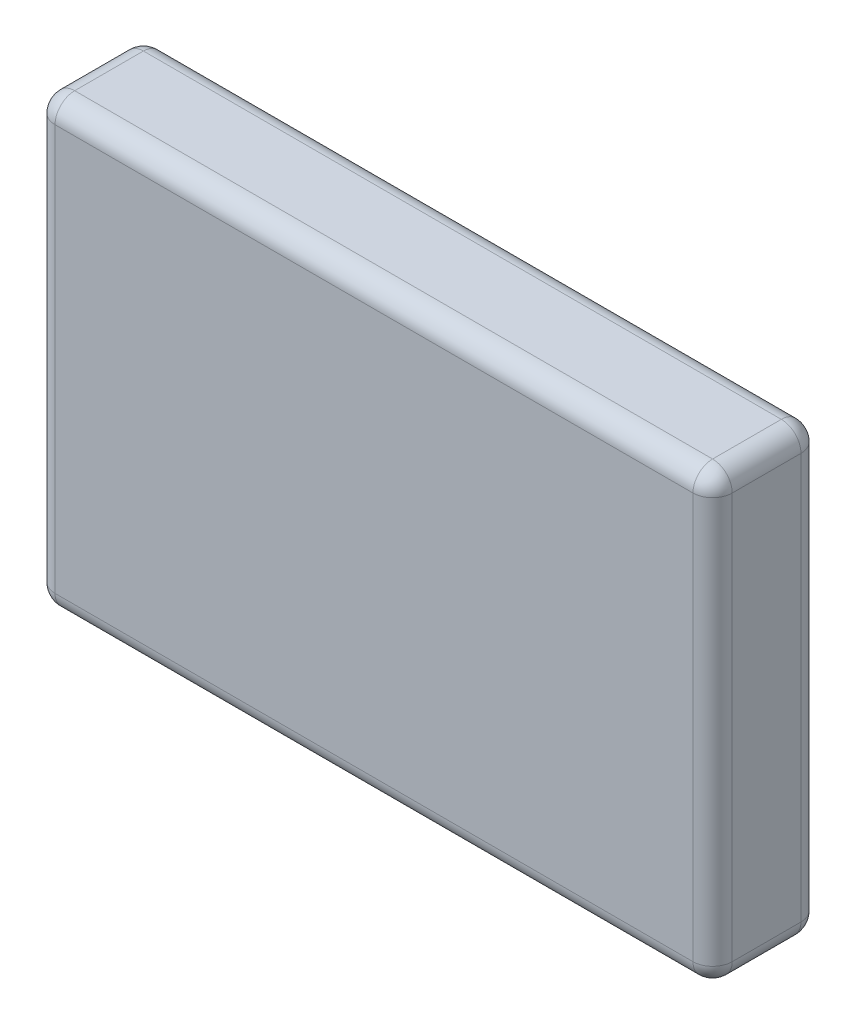
SolidWorks part; units mm, degrees
ref_plane "Front Plane" through (0, 0, 0) normal (0, 0, 1) x (1, 0, 0)
ref_plane "Top Plane" through (0, 0, 0) normal (0, 1, 0) x (1, 0, 0)
ref_plane "Right Plane" through (0, 0, 0) normal (1, 0, 0) x (0, 0, -1)
sketch "Sketch1" plane through (0, 0, 0) normal (0, 0, 1) x (1, 0, 0)
  line L1 (-103.45, 68) -> (103.45, 68)
  line L2 (-103.45, 68) -> (-103.45, -68)
  line L3 (-103.45, -68) -> (103.45, -68)
  line L4 (103.45, 68) -> (103.45, -68)
  line L5 (-103.45, 68) -> (103.45, -68) construction
  line L6 (-103.45, -68) -> (103.45, 68) construction
  point P0 (0, 0)
  dimension "D1" = 206.9
  dimension "D2" = 136
extrude "Boss-Extrude1" add sketch "Sketch1" along normal blind 33
fillet "Fillet1" radius 6 12 edges at (0, -68, 33) (-103.45, 0, 33) (0, 68, 33) (103.45, 0, 33) (103.45, 0, 0) (0, 68, 0) (0, -68, 0) (-103.45, 0, 0) (-103.45, 68, 16.5) (103.45, 68, 16.5) (103.45, -68, 16.5) (-103.45, -68, 16.5)
sketch "Sketch2" plane through (-103.45, 0, 0) normal (-1, 0, 0) x (0, 0, 1)
  line L0 (27, -68) -> (6, -68) construction
  line L1 (23, -30) -> (7, -30)
  line L2 (23, -30) -> (23, -59.3264)
  line L3 (23, -59.3264) -> (7, -59.3264)
  line L4 (7, -30) -> (7, -59.3264)
  line L5 (23, -30) -> (7, -59.3264) construction
  line L6 (23, -59.3264) -> (7, -30) construction
  line L7 (0, -62) -> (0, 62) construction
  point P0 (15, -44.6632)
  point P7 (16.5, -68)
  dimension "D1" = 38
  dimension "D2" = 7
  dimension "D3" = 16
extrude "Cut-Extrude1" cut sketch "Sketch2" against normal blind 36
sketch "Sketch3" plane through (-103.45, 0, 0) normal (-1, 0, 0) x (0, 0, 1)
  line L0 (23, -30) -> (7, -30) construction
  line L1 (33, 62) -> (33, -62) construction
  circle A0 centre (16.75, -17.5) radius 3.25
  point P4 (15, -30)
  dimension "D1" = 6.5
  dimension "D2" = 12.5
  dimension "D3" = 16.25
extrude "Cut-Extrude2" cut sketch "Sketch3" against normal blind 36
sketch "Sketch4" plane through (-103.45, 0, 0) normal (-1, 0, 0) x (0, 0, 1)
  line L0 (6, 68) -> (27, 68) construction
  line L1 (33, 62) -> (33, -62) construction
  circle A0 centre (16.5, 20) radius 8
  dimension "D1" = 48
  dimension "D2" = 16
  dimension "D3" = 16.5
extrude "Cut-Extrude3" cut sketch "Sketch4" against normal blind 36
